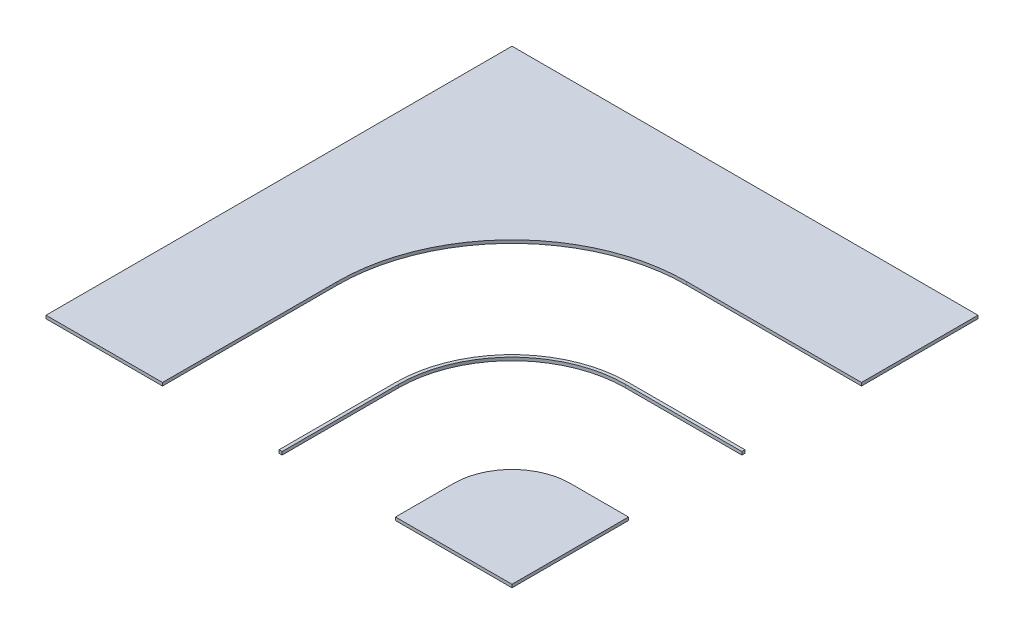
SolidWorks part; units mm, degrees
ref_plane "Front Plane" through (0, 0, 0) normal (0, 0, 1) x (1, 0, 0)
ref_plane "Top Plane" through (0, 0, 0) normal (0, 1, 0) x (1, 0, 0)
ref_plane "Right Plane" through (0, 0, 0) normal (1, 0, 0) x (0, 0, -1)
sketch "Sketch1" plane through (0, 0, 0) normal (0, 1, 0) x (1, 0, 0)
  line L1 (-750, -750) -> (750, -750)
  line L2 (-750, -750) -> (-750, 750)
  line L3 (-750, 750) -> (750, 750)
  line L4 (750, -750) -> (750, -375)
  line L7 (-375, -750) -> (375, -750)
  line L9 (-375, 750) -> (375, 750)
  line L11 (375, 375) -> (379.9178, 375)
  line L12 (-379.9178, 375) -> (-375, 375)
  line L13 (-750, 379.9178) -> (-750, -370.0822)
  line L15 (750, 375) -> (750, -2.4349)
  line L18 (0, -750) -> (750, -750)
  line L19 (750, 0) -> (750, -2.4349)
  line L20 (750, -2.4349) -> (752.4428, -0.008) construction
  line L21 (0, -750) -> (750, -750)
  line L22 (4.9178, -375) -> (4.95, -375)
  line L23 (750, 0) -> (750, -2.4349)
  line L24 (562.5, -375) -> (750, -375)
  line L26 (375, 375) -> (379.9178, 375)
  line L27 (750, -2.4349) -> (750, -375)
  line L29 (-375, -750) -> (750, -750)
  line L30 (750, 375) -> (750, -2.4349)
  line L33 (375, -750) -> (750, -750)
  line L34 (750, -375) -> (750, -750)
  line L35 (187.5, 375) -> (750, 375)
  line L36 (-375, -187.5) -> (-375, -750)
  line L37 (-375, -750) -> (750, -750)
  line L38 (750, 375) -> (750, -2.4349)
  line L41 (0, -750) -> (750, -750)
  line L42 (750, 0) -> (750, -2.4349)
  line L43 (562.5, -375) -> (750, -375)
  line L44 (375, -562.5) -> (375, -750)
  line L45 (375, -750) -> (750, -750)
  line L46 (750, -375) -> (750, -750)
  line L47 (109.835, -109.835) -> (108.997, -113.9549)
  line L49 (750, -2.4349) -> (750, 750)
  line L50 (750, -375) -> (750, -750)
  line L51 (750, -375) -> (750, -750)
  line L52 (750, -375) -> (750, -750)
  line L53 (750, -375) -> (750, -750)
  line L54 (750, -375) -> (750, -750)
  arc A12 (187.5, 375) -> (-375, -187.5) centre (187.5, -187.5) ccw
  arc A17 (562.5, -375) -> (375, -562.5) centre (562.5, -562.5) ccw
  point P0 (0, 0)
  point P11 (0, 750)
  point P18 (-750, 0)
  dimension "D1" = 1500
  dimension "D2" = 750
extrude "Boss-Extrude1" add sketch "Sketch1" along normal blind 10 contours A12 L35 L11 L49 L3 L2 L1 L36 | L24 A17 L44 L1 L4 region at (-241.606, 0, -241.606) region at (570.7554, 0, 570.7554)
sketch "Sketch2" plane through (0, 0, 0) normal (0, 1, 0) x (1, 0, 0)
  line L1 (375, 0) -> (750, 0)
  line L2 (0, -375) -> (0, -750)
  arc A1 (375, 0) -> (0, -375) centre (375, -375) ccw
extrude "Extrude-Thin1" add sketch "Sketch2" along normal blind 10 separate body thin thin type one direction wall 10
equation "\"Scale\"= 8"
equation "\"Tile Size\"= \"Road Size\" * 2"
equation "\"D1@Sketch1\"=\"Tile Size\""
equation "\"Road Size\"= \"Real Lane Size\" * 2 / \"Scale\""
equation "\"Real Lane Size\"= 3m"
